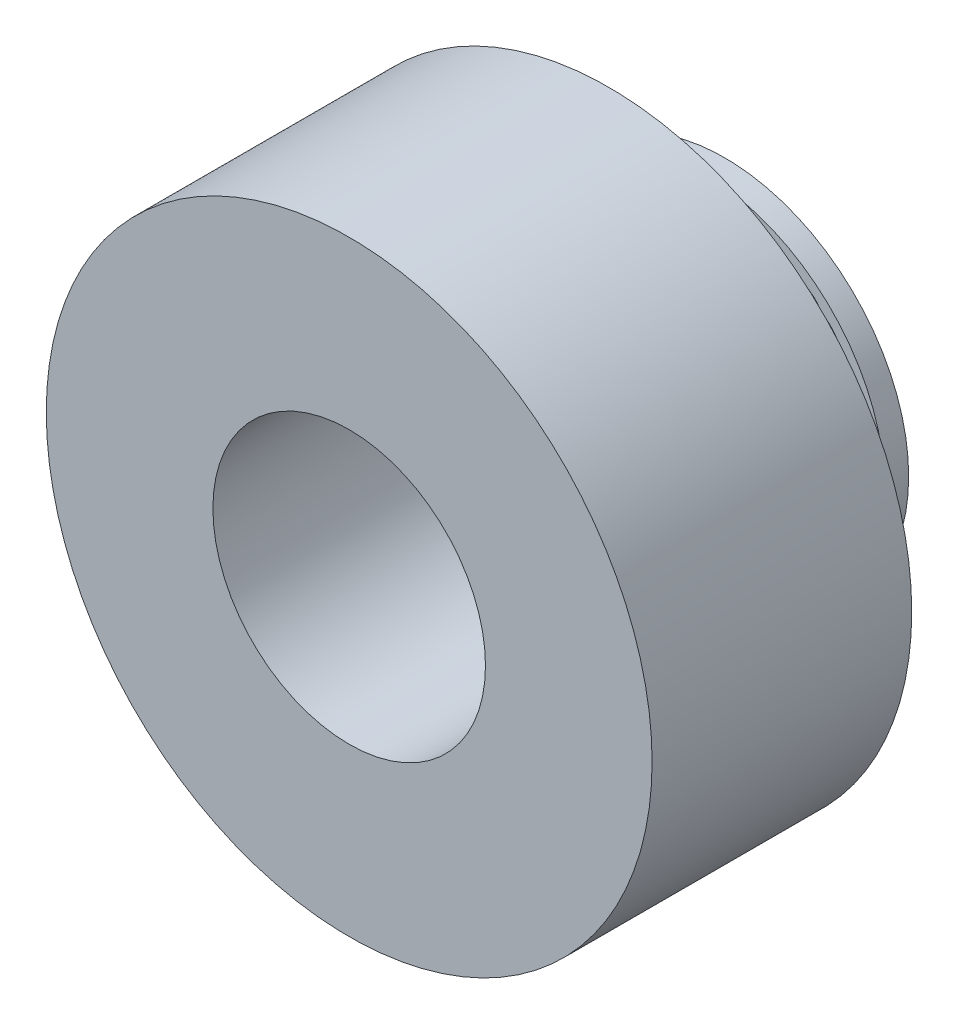
SolidWorks part; units mm, degrees
ref_plane "Front Plane" through (0, 0, 0) normal (0, 0, 1) x (1, 0, 0)
ref_plane "Top Plane" through (0, 0, 0) normal (0, 1, 0) x (1, 0, 0)
ref_plane "Right Plane" through (0, 0, 0) normal (1, 0, 0) x (0, 0, -1)
sketch "Sketch1" plane through (0, 0, 0) normal (0, 0, 1) x (1, 0, 0)
  line L0 (-50.7835, 0) -> (-50.3466, 0)
  line L5 (-50.2571, 0.0627) -> (-50.1641, 0.3183)
  line L6 (-50.0746, 0.381) -> (-49.4934, 0.381)
  line L7 (-49.784, 0.381) -> (-49.784, 0) construction
  line L8 (-49.3109, 0.0627) -> (-49.4039, 0.3183)
  line L39 (-51.2936, 0.1442) -> (-51.3455, 0.4113)
  line L40 (-50.2571, 0.0627) -> (-49.3109, 0.0627) construction
  line L56 (-49.2214, 0) -> (-48.7845, 0)
  line L60 (-51.9981, 0.5781) -> (-51.4241, 0.4872)
  line L61 (-52.2282, 0.2923) -> (-52.0963, 0.5302)
  line L62 (-52.7579, 0.3127) -> (-52.3264, 0.2444)
  line L63 (-51.215, 0.0683) -> (-50.7835, 0)
  line L64 (-53.2392, 0.535) -> (-53.2487, 0.8069)
  line L65 (-53.8671, 1.0737) -> (-53.3144, 0.8941)
  line L66 (-54.1391, 0.8274) -> (-53.9716, 1.0418)
  line L67 (-54.6591, 0.9304) -> (-54.2436, 0.7954)
  line L68 (-53.1734, 0.4477) -> (-52.7579, 0.3127)
  line L69 (-55.0997, 1.2253) -> (-55.0665, 1.4953)
  line L70 (-55.6356, 1.8556) -> (-55.1178, 1.5918)
  line L71 (-55.9428, 1.6549) -> (-55.7438, 1.8404)
  line L72 (-56.4403, 1.838) -> (-56.051, 1.6396)
  line L73 (-55.0484, 1.1288) -> (-54.6591, 0.9304)
  line L74 (-56.8293, 2.1981) -> (-56.7543, 2.4596)
  line L75 (-57.26, 2.9045) -> (-56.7898, 2.5629)
  line L76 (-57.5948, 2.7543) -> (-57.3693, 2.9064)
  line L77 (-58.0575, 3.013) -> (-57.7041, 2.7562)
  line L78 (-56.7937, 2.0948) -> (-56.4403, 1.838)
  line L79 (-58.3854, 3.4295) -> (-58.2704, 3.6761)
  line L80 (-58.7003, 4.1946) -> (-58.2894, 3.7837)
  line L81 (-59.0545, 4.0986) -> (-58.8079, 4.2136)
  line L82 (-59.471, 4.4265) -> (-59.1621, 4.1176)
  line L83 (-58.3664, 3.3219) -> (-58.0575, 3.013)
  line L84 (-59.7297, 4.8892) -> (-59.5776, 5.1147)
  line L85 (-59.9211, 5.6942) -> (-59.5795, 5.224)
  line L86 (-60.2859, 5.6547) -> (-60.0244, 5.7297)
  line L87 (-60.646, 6.0437) -> (-60.3892, 5.6903)
  line L88 (-59.7278, 4.7799) -> (-59.471, 4.4265)
  line L89 (-60.8291, 6.5412) -> (-60.6436, 6.7402)
  line L90 (-60.8922, 7.3662) -> (-60.6284, 6.8484)
  line L91 (-61.2587, 7.3843) -> (-60.9887, 7.4175)
  line L92 (-61.5536, 7.8249) -> (-61.3552, 7.4356)
  line L93 (-60.8444, 6.433) -> (-60.646, 6.0437)
  line L94 (-61.6566, 8.3449) -> (-61.4422, 8.5124)
  line L95 (-61.5899, 9.1696) -> (-61.4103, 8.6169)
  line L96 (-61.949, 9.2448) -> (-61.6771, 9.2353)
  line L97 (-62.1713, 9.7261) -> (-62.0363, 9.3106)
  line L98 (-61.6886, 8.2404) -> (-61.5536, 7.8249)
  line L99 (-62.1917, 10.2558) -> (-61.9538, 10.3877)
  line L100 (-61.9968, 11.0599) -> (-61.9059, 10.4859)
  line L101 (-62.3398, 11.1904) -> (-62.0727, 11.1385)
  line L102 (-62.484, 11.7005) -> (-62.4157, 11.269)
  line L103 (-62.2396, 10.1576) -> (-62.1713, 9.7261)
  line L104 (-62.4213, 12.2269) -> (-62.1657, 12.3199)
  line L105 (-62.103, 12.9906) -> (-62.103, 12.4094)
  line L106 (-62.4213, 13.1731) -> (-62.1657, 13.0801)
  line L107 (-62.484, 13.6995) -> (-62.484, 13.2626)
  line L108 (-62.484, 12.1374) -> (-62.484, 11.7005)
  line L109 (-62.3398, 14.2096) -> (-62.0727, 14.2615)
  line L110 (-61.9059, 14.9141) -> (-61.9968, 14.3401)
  line L111 (-62.1917, 15.1442) -> (-61.9538, 15.0123)
  line L112 (-62.1713, 15.6739) -> (-62.2396, 15.2424)
  line L113 (-62.4157, 14.131) -> (-62.484, 13.6995)
  line L114 (-61.949, 16.1552) -> (-61.6771, 16.1647)
  line L115 (-61.4103, 16.7831) -> (-61.5899, 16.2304)
  line L116 (-61.6566, 17.0551) -> (-61.4422, 16.8876)
  line L117 (-61.5536, 17.5751) -> (-61.6886, 17.1596)
  line L118 (-62.0363, 16.0894) -> (-62.1713, 15.6739)
  line L119 (-61.2587, 18.0157) -> (-60.9887, 17.9825)
  line L120 (-60.6284, 18.5516) -> (-60.8922, 18.0338)
  line L121 (-60.8291, 18.8588) -> (-60.6436, 18.6598)
  line L122 (-60.646, 19.3563) -> (-60.8444, 18.967)
  line L123 (-61.3552, 17.9644) -> (-61.5536, 17.5751)
  line L124 (-60.2859, 19.7453) -> (-60.0244, 19.6703)
  line L125 (-59.5795, 20.176) -> (-59.9211, 19.7058)
  line L126 (-59.7297, 20.5108) -> (-59.5776, 20.2853)
  line L127 (-59.471, 20.9735) -> (-59.7278, 20.6201)
  line L128 (-60.3892, 19.7097) -> (-60.646, 19.3563)
  line L129 (-59.0545, 21.3014) -> (-58.8079, 21.1864)
  line L130 (-58.2894, 21.6163) -> (-58.7003, 21.2054)
  line L131 (-58.3854, 21.9705) -> (-58.2704, 21.7239)
  line L132 (-58.0575, 22.387) -> (-58.3664, 22.0781)
  line L133 (-59.1621, 21.2824) -> (-59.471, 20.9735)
  line L134 (-57.5948, 22.6457) -> (-57.3693, 22.4936)
  line L135 (-56.7898, 22.8371) -> (-57.26, 22.4955)
  line L136 (-56.8293, 23.2019) -> (-56.7543, 22.9404)
  line L137 (-56.4403, 23.562) -> (-56.7937, 23.3052)
  line L138 (-57.7041, 22.6438) -> (-58.0575, 22.387)
  line L139 (-55.9428, 23.7451) -> (-55.7438, 23.5596)
  line L140 (-55.1178, 23.8082) -> (-55.6356, 23.5444)
  line L141 (-55.0997, 24.1747) -> (-55.0665, 23.9047)
  line L142 (-54.6591, 24.4696) -> (-55.0484, 24.2712)
  line L143 (-56.051, 23.7604) -> (-56.4403, 23.562)
  line L144 (-54.1391, 24.5726) -> (-53.9716, 24.3582)
  line L145 (-53.3144, 24.5059) -> (-53.8671, 24.3263)
  line L146 (-53.2392, 24.865) -> (-53.2487, 24.5931)
  line L147 (-52.7579, 25.0873) -> (-53.1734, 24.9523)
  line L148 (-54.2436, 24.6046) -> (-54.6591, 24.4696)
  line L149 (-52.2282, 25.1077) -> (-52.0963, 24.8698)
  line L150 (-51.4241, 24.9128) -> (-51.9981, 24.8219)
  line L151 (-51.2936, 25.2558) -> (-51.3455, 24.9887)
  line L152 (-50.7835, 25.4) -> (-51.215, 25.3317)
  line L153 (-52.3264, 25.1556) -> (-52.7579, 25.0873)
  line L154 (-50.2571, 25.3373) -> (-50.1641, 25.0817)
  line L155 (-49.4934, 25.019) -> (-50.0746, 25.019)
  line L156 (-49.3109, 25.3373) -> (-49.4039, 25.0817)
  line L157 (-48.7845, 25.4) -> (-49.2214, 25.4)
  line L158 (-50.3466, 25.4) -> (-50.7835, 25.4)
  line L159 (-48.2744, 25.2558) -> (-48.2225, 24.9887)
  line L160 (-47.5699, 24.8219) -> (-48.1439, 24.9128)
  line L161 (-47.3398, 25.1077) -> (-47.4717, 24.8698)
  line L162 (-46.8101, 25.0873) -> (-47.2416, 25.1556)
  line L163 (-48.353, 25.3317) -> (-48.7845, 25.4)
  line L164 (-46.3288, 24.865) -> (-46.3193, 24.5931)
  line L165 (-45.7009, 24.3263) -> (-46.2536, 24.5059)
  line L166 (-45.4289, 24.5726) -> (-45.5964, 24.3582)
  line L167 (-44.9089, 24.4696) -> (-45.3244, 24.6046)
  line L168 (-46.3946, 24.9523) -> (-46.8101, 25.0873)
  line L169 (-44.4683, 24.1747) -> (-44.5015, 23.9047)
  line L170 (-43.9324, 23.5444) -> (-44.4502, 23.8082)
  line L171 (-43.6252, 23.7451) -> (-43.8242, 23.5596)
  line L172 (-43.1277, 23.562) -> (-43.517, 23.7604)
  line L173 (-44.5196, 24.2712) -> (-44.9089, 24.4696)
  line L174 (-42.7387, 23.2019) -> (-42.8137, 22.9404)
  line L175 (-42.308, 22.4955) -> (-42.7782, 22.8371)
  line L176 (-41.9732, 22.6457) -> (-42.1987, 22.4936)
  line L177 (-41.5105, 22.387) -> (-41.8639, 22.6438)
  line L178 (-42.7743, 23.3052) -> (-43.1277, 23.562)
  line L179 (-41.1826, 21.9705) -> (-41.2976, 21.7239)
  line L180 (-40.8677, 21.2054) -> (-41.2786, 21.6163)
  line L181 (-40.5135, 21.3014) -> (-40.7601, 21.1864)
  line L182 (-40.097, 20.9735) -> (-40.4059, 21.2824)
  line L183 (-41.2016, 22.0781) -> (-41.5105, 22.387)
  line L184 (-39.8383, 20.5108) -> (-39.9904, 20.2853)
  line L185 (-39.6469, 19.7058) -> (-39.9885, 20.176)
  line L186 (-39.2821, 19.7453) -> (-39.5436, 19.6703)
  line L187 (-38.922, 19.3563) -> (-39.1788, 19.7097)
  line L188 (-39.8402, 20.6201) -> (-40.097, 20.9735)
  line L189 (-38.7389, 18.8588) -> (-38.9244, 18.6598)
  line L190 (-38.6758, 18.0338) -> (-38.9396, 18.5516)
  line L191 (-38.3093, 18.0157) -> (-38.5793, 17.9825)
  line L192 (-38.0144, 17.5751) -> (-38.2128, 17.9644)
  line L193 (-38.7236, 18.967) -> (-38.922, 19.3563)
  line L194 (-37.9114, 17.0551) -> (-38.1258, 16.8876)
  line L195 (-37.9781, 16.2304) -> (-38.1577, 16.7831)
  line L196 (-37.619, 16.1552) -> (-37.8909, 16.1647)
  line L197 (-37.3967, 15.6739) -> (-37.5317, 16.0894)
  line L198 (-37.8794, 17.1596) -> (-38.0144, 17.5751)
  line L199 (-37.3763, 15.1442) -> (-37.6142, 15.0123)
  line L200 (-37.5712, 14.3401) -> (-37.6621, 14.9141)
  line L201 (-37.2282, 14.2096) -> (-37.4953, 14.2615)
  line L202 (-37.084, 13.6995) -> (-37.1523, 14.131)
  line L203 (-37.3284, 15.2424) -> (-37.3967, 15.6739)
  line L204 (-37.1467, 13.1731) -> (-37.4023, 13.0801)
  line L205 (-37.465, 12.4094) -> (-37.465, 12.9906)
  line L206 (-37.1467, 12.2269) -> (-37.4023, 12.3199)
  line L207 (-37.084, 11.7005) -> (-37.084, 12.1374)
  line L208 (-37.084, 13.2626) -> (-37.084, 13.6995)
  line L209 (-37.2282, 11.1904) -> (-37.4953, 11.1385)
  line L210 (-37.6621, 10.4859) -> (-37.5712, 11.0599)
  line L211 (-37.3763, 10.2558) -> (-37.6142, 10.3877)
  line L212 (-37.3967, 9.7261) -> (-37.3284, 10.1576)
  line L213 (-37.1523, 11.269) -> (-37.084, 11.7005)
  line L214 (-37.619, 9.2448) -> (-37.8909, 9.2353)
  line L215 (-38.1577, 8.6169) -> (-37.9781, 9.1696)
  line L216 (-37.9114, 8.3449) -> (-38.1258, 8.5124)
  line L217 (-38.0144, 7.8249) -> (-37.8794, 8.2404)
  line L218 (-37.5317, 9.3106) -> (-37.3967, 9.7261)
  line L219 (-38.3093, 7.3843) -> (-38.5793, 7.4175)
  line L220 (-38.9396, 6.8484) -> (-38.6758, 7.3662)
  line L221 (-38.7389, 6.5412) -> (-38.9244, 6.7402)
  line L222 (-38.922, 6.0437) -> (-38.7236, 6.433)
  line L223 (-38.2128, 7.4356) -> (-38.0144, 7.8249)
  line L224 (-39.2821, 5.6547) -> (-39.5436, 5.7297)
  line L225 (-39.9885, 5.224) -> (-39.6469, 5.6942)
  line L226 (-39.8383, 4.8892) -> (-39.9904, 5.1147)
  line L227 (-40.097, 4.4265) -> (-39.8402, 4.7799)
  line L228 (-39.1788, 5.6903) -> (-38.922, 6.0437)
  line L229 (-40.5135, 4.0986) -> (-40.7601, 4.2136)
  line L230 (-41.2786, 3.7837) -> (-40.8677, 4.1946)
  line L231 (-41.1826, 3.4295) -> (-41.2976, 3.6761)
  line L232 (-41.5105, 3.013) -> (-41.2016, 3.3219)
  line L233 (-40.4059, 4.1176) -> (-40.097, 4.4265)
  line L234 (-41.9732, 2.7543) -> (-42.1987, 2.9064)
  line L235 (-42.7782, 2.5629) -> (-42.308, 2.9045)
  line L236 (-42.7387, 2.1981) -> (-42.8137, 2.4596)
  line L237 (-43.1277, 1.838) -> (-42.7743, 2.0948)
  line L238 (-41.8639, 2.7562) -> (-41.5105, 3.013)
  line L239 (-43.6252, 1.6549) -> (-43.8242, 1.8404)
  line L240 (-44.4502, 1.5918) -> (-43.9324, 1.8556)
  line L241 (-44.4683, 1.2253) -> (-44.5015, 1.4953)
  line L242 (-44.9089, 0.9304) -> (-44.5196, 1.1288)
  line L243 (-43.517, 1.6396) -> (-43.1277, 1.838)
  line L244 (-45.4289, 0.8274) -> (-45.5964, 1.0418)
  line L245 (-46.2536, 0.8941) -> (-45.7009, 1.0737)
  line L246 (-46.3288, 0.535) -> (-46.3193, 0.8069)
  line L247 (-46.8101, 0.3127) -> (-46.3946, 0.4477)
  line L248 (-45.3244, 0.7954) -> (-44.9089, 0.9304)
  line L249 (-47.3398, 0.2923) -> (-47.4717, 0.5302)
  line L250 (-48.1439, 0.4872) -> (-47.5699, 0.5781)
  line L251 (-48.2744, 0.1442) -> (-48.2225, 0.4113)
  line L252 (-48.7845, 0) -> (-48.353, 0.0683)
  line L253 (-47.2416, 0.2444) -> (-46.8101, 0.3127)
  arc A0 (-50.3466, 0) -> (-50.2571, 0.0627) centre (-50.3466, 0.0952) ccw
  arc A1 (-50.1641, 0.3183) -> (-50.0746, 0.381) centre (-50.0746, 0.2857) cw
  arc A2 (-49.4039, 0.3183) -> (-49.4934, 0.381) centre (-49.4934, 0.2857) ccw
  arc A3 (-49.2214, 0) -> (-49.3109, 0.0627) centre (-49.2214, 0.0952) cw
  arc A4 (-51.215, 0.0683) -> (-51.2936, 0.1442) centre (-51.2001, 0.1624) cw
  arc A5 (-51.3455, 0.4113) -> (-51.4241, 0.4872) centre (-51.439, 0.3931) ccw
  arc A6 (-52.0963, 0.5302) -> (-51.9981, 0.5781) centre (-52.013, 0.484) cw
  arc A7 (-52.3264, 0.2444) -> (-52.2282, 0.2923) centre (-52.3115, 0.3385) ccw
  arc A8 (-53.1734, 0.4477) -> (-53.2392, 0.535) centre (-53.144, 0.5383) cw
  arc A9 (-53.2487, 0.8069) -> (-53.3144, 0.8941) centre (-53.3439, 0.8036) ccw
  arc A10 (-53.9716, 1.0418) -> (-53.8671, 1.0737) centre (-53.8966, 0.9831) cw
  arc A11 (-54.2436, 0.7954) -> (-54.1391, 0.8274) centre (-54.2142, 0.886) ccw
  arc A12 (-55.0484, 1.1288) -> (-55.0997, 1.2253) centre (-55.0051, 1.2137) cw
  arc A13 (-55.0665, 1.4953) -> (-55.1178, 1.5918) centre (-55.1611, 1.5069) ccw
  arc A14 (-55.7438, 1.8404) -> (-55.6356, 1.8556) centre (-55.6789, 1.7707) cw
  arc A15 (-56.051, 1.6396) -> (-55.9428, 1.6549) centre (-56.0077, 1.7245) ccw
  arc A16 (-56.7937, 2.0948) -> (-56.8293, 2.1981) centre (-56.7377, 2.1718) cw
  arc A17 (-56.7543, 2.4596) -> (-56.7898, 2.5629) centre (-56.8458, 2.4859) ccw
  arc A18 (-57.3693, 2.9064) -> (-57.26, 2.9045) centre (-57.316, 2.8275) cw
  arc A19 (-57.7041, 2.7562) -> (-57.5948, 2.7543) centre (-57.6481, 2.8333) ccw
  arc A20 (-58.3664, 3.3219) -> (-58.3854, 3.4295) centre (-58.2991, 3.3893) cw
  arc A21 (-58.2704, 3.6761) -> (-58.2894, 3.7837) centre (-58.3567, 3.7163) ccw
  arc A22 (-58.8079, 4.2136) -> (-58.7003, 4.1946) centre (-58.7677, 4.1273) cw
  arc A23 (-59.1621, 4.1176) -> (-59.0545, 4.0986) centre (-59.0947, 4.1849) ccw
  arc A24 (-59.7278, 4.7799) -> (-59.7297, 4.8892) centre (-59.6507, 4.8359) cw
  arc A25 (-59.5776, 5.1147) -> (-59.5795, 5.224) centre (-59.6565, 5.168) ccw
  arc A26 (-60.0244, 5.7297) -> (-59.9211, 5.6942) centre (-59.9981, 5.6382) cw
  arc A27 (-60.3892, 5.6903) -> (-60.2859, 5.6547) centre (-60.3122, 5.7463) ccw
  arc A28 (-60.8444, 6.433) -> (-60.8291, 6.5412) centre (-60.7595, 6.4763) cw
  arc A29 (-60.6436, 6.7402) -> (-60.6284, 6.8484) centre (-60.7133, 6.8051) ccw
  arc A30 (-60.9887, 7.4175) -> (-60.8922, 7.3662) centre (-60.9771, 7.3229) cw
  arc A31 (-61.3552, 7.4356) -> (-61.2587, 7.3843) centre (-61.2703, 7.4789) ccw
  arc A32 (-61.6886, 8.2404) -> (-61.6566, 8.3449) centre (-61.598, 8.2698) cw
  arc A33 (-61.4422, 8.5124) -> (-61.4103, 8.6169) centre (-61.5009, 8.5874) ccw
  arc A34 (-61.6771, 9.2353) -> (-61.5899, 9.1696) centre (-61.6804, 9.1401) cw
  arc A35 (-62.0363, 9.3106) -> (-61.949, 9.2448) centre (-61.9457, 9.34) ccw
  arc A36 (-62.2396, 10.1576) -> (-62.1917, 10.2558) centre (-62.1455, 10.1725) cw
  arc A37 (-61.9538, 10.3877) -> (-61.9059, 10.4859) centre (-62, 10.471) ccw
  arc A38 (-62.0727, 11.1385) -> (-61.9968, 11.0599) centre (-62.0909, 11.045) cw
  arc A39 (-62.4157, 11.269) -> (-62.3398, 11.1904) centre (-62.3216, 11.2839) ccw
  arc A40 (-62.484, 12.1374) -> (-62.4213, 12.2269) centre (-62.3888, 12.1374) cw
  arc A41 (-62.1657, 12.3199) -> (-62.103, 12.4094) centre (-62.1983, 12.4094) ccw
  arc A42 (-62.1657, 13.0801) -> (-62.103, 12.9906) centre (-62.1983, 12.9906) cw
  arc A43 (-62.484, 13.2626) -> (-62.4213, 13.1731) centre (-62.3888, 13.2626) ccw
  arc A44 (-62.4157, 14.131) -> (-62.3398, 14.2096) centre (-62.3216, 14.1161) cw
  arc A45 (-62.0727, 14.2615) -> (-61.9968, 14.3401) centre (-62.0909, 14.355) ccw
  arc A46 (-61.9538, 15.0123) -> (-61.9059, 14.9141) centre (-62, 14.929) cw
  arc A47 (-62.2396, 15.2424) -> (-62.1917, 15.1442) centre (-62.1455, 15.2275) ccw
  arc A48 (-62.0363, 16.0894) -> (-61.949, 16.1552) centre (-61.9457, 16.06) cw
  arc A49 (-61.6771, 16.1647) -> (-61.5899, 16.2304) centre (-61.6804, 16.2599) ccw
  arc A50 (-61.4422, 16.8876) -> (-61.4103, 16.7831) centre (-61.5009, 16.8126) cw
  arc A51 (-61.6886, 17.1596) -> (-61.6566, 17.0551) centre (-61.598, 17.1302) ccw
  arc A52 (-61.3552, 17.9644) -> (-61.2587, 18.0157) centre (-61.2703, 17.9211) cw
  arc A53 (-60.9887, 17.9825) -> (-60.8922, 18.0338) centre (-60.9771, 18.0771) ccw
  arc A54 (-60.6436, 18.6598) -> (-60.6284, 18.5516) centre (-60.7133, 18.5949) cw
  arc A55 (-60.8444, 18.967) -> (-60.8291, 18.8588) centre (-60.7595, 18.9237) ccw
  arc A56 (-60.3892, 19.7097) -> (-60.2859, 19.7453) centre (-60.3122, 19.6537) cw
  arc A57 (-60.0244, 19.6703) -> (-59.9211, 19.7058) centre (-59.9981, 19.7618) ccw
  arc A58 (-59.5776, 20.2853) -> (-59.5795, 20.176) centre (-59.6565, 20.232) cw
  arc A59 (-59.7278, 20.6201) -> (-59.7297, 20.5108) centre (-59.6507, 20.5641) ccw
  arc A60 (-59.1621, 21.2824) -> (-59.0545, 21.3014) centre (-59.0947, 21.2151) cw
  arc A61 (-58.8079, 21.1864) -> (-58.7003, 21.2054) centre (-58.7677, 21.2727) ccw
  arc A62 (-58.2704, 21.7239) -> (-58.2894, 21.6163) centre (-58.3567, 21.6837) cw
  arc A63 (-58.3664, 22.0781) -> (-58.3854, 21.9705) centre (-58.2991, 22.0107) ccw
  arc A64 (-57.7041, 22.6438) -> (-57.5948, 22.6457) centre (-57.6481, 22.5667) cw
  arc A65 (-57.3693, 22.4936) -> (-57.26, 22.4955) centre (-57.316, 22.5725) ccw
  arc A66 (-56.7543, 22.9404) -> (-56.7898, 22.8371) centre (-56.8458, 22.9141) cw
  arc A67 (-56.7937, 23.3052) -> (-56.8293, 23.2019) centre (-56.7377, 23.2282) ccw
  arc A68 (-56.051, 23.7604) -> (-55.9428, 23.7451) centre (-56.0077, 23.6755) cw
  arc A69 (-55.7438, 23.5596) -> (-55.6356, 23.5444) centre (-55.6789, 23.6293) ccw
  arc A70 (-55.0665, 23.9047) -> (-55.1178, 23.8082) centre (-55.1611, 23.8931) cw
  arc A71 (-55.0484, 24.2712) -> (-55.0997, 24.1747) centre (-55.0051, 24.1863) ccw
  arc A72 (-54.2436, 24.6046) -> (-54.1391, 24.5726) centre (-54.2142, 24.514) cw
  arc A73 (-53.9716, 24.3582) -> (-53.8671, 24.3263) centre (-53.8966, 24.4169) ccw
  arc A74 (-53.2487, 24.5931) -> (-53.3144, 24.5059) centre (-53.3439, 24.5964) cw
  arc A75 (-53.1734, 24.9523) -> (-53.2392, 24.865) centre (-53.144, 24.8617) ccw
  arc A76 (-52.3264, 25.1556) -> (-52.2282, 25.1077) centre (-52.3115, 25.0615) cw
  arc A77 (-52.0963, 24.8698) -> (-51.9981, 24.8219) centre (-52.013, 24.916) ccw
  arc A78 (-51.3455, 24.9887) -> (-51.4241, 24.9128) centre (-51.439, 25.0069) cw
  arc A79 (-51.215, 25.3317) -> (-51.2936, 25.2558) centre (-51.2001, 25.2376) ccw
  arc A80 (-50.3466, 25.4) -> (-50.2571, 25.3373) centre (-50.3466, 25.3048) cw
  arc A81 (-50.1641, 25.0817) -> (-50.0746, 25.019) centre (-50.0746, 25.1143) ccw
  arc A82 (-49.4039, 25.0817) -> (-49.4934, 25.019) centre (-49.4934, 25.1143) cw
  arc A83 (-49.2214, 25.4) -> (-49.3109, 25.3373) centre (-49.2214, 25.3048) ccw
  arc A84 (-48.353, 25.3317) -> (-48.2744, 25.2558) centre (-48.3679, 25.2376) cw
  arc A85 (-48.2225, 24.9887) -> (-48.1439, 24.9128) centre (-48.129, 25.0069) ccw
  arc A86 (-47.4717, 24.8698) -> (-47.5699, 24.8219) centre (-47.555, 24.916) cw
  arc A87 (-47.2416, 25.1556) -> (-47.3398, 25.1077) centre (-47.2565, 25.0615) ccw
  arc A88 (-46.3946, 24.9523) -> (-46.3288, 24.865) centre (-46.424, 24.8617) cw
  arc A89 (-46.3193, 24.5931) -> (-46.2536, 24.5059) centre (-46.2241, 24.5964) ccw
  arc A90 (-45.5964, 24.3582) -> (-45.7009, 24.3263) centre (-45.6714, 24.4169) cw
  arc A91 (-45.3244, 24.6046) -> (-45.4289, 24.5726) centre (-45.3538, 24.514) ccw
  arc A92 (-44.5196, 24.2712) -> (-44.4683, 24.1747) centre (-44.5629, 24.1863) cw
  arc A93 (-44.5015, 23.9047) -> (-44.4502, 23.8082) centre (-44.4069, 23.8931) ccw
  arc A94 (-43.8242, 23.5596) -> (-43.9324, 23.5444) centre (-43.8891, 23.6293) cw
  arc A95 (-43.517, 23.7604) -> (-43.6252, 23.7451) centre (-43.5603, 23.6755) ccw
  arc A96 (-42.7743, 23.3052) -> (-42.7387, 23.2019) centre (-42.8303, 23.2282) cw
  arc A97 (-42.8137, 22.9404) -> (-42.7782, 22.8371) centre (-42.7222, 22.9141) ccw
  arc A98 (-42.1987, 22.4936) -> (-42.308, 22.4955) centre (-42.252, 22.5725) cw
  arc A99 (-41.8639, 22.6438) -> (-41.9732, 22.6457) centre (-41.9199, 22.5667) ccw
  arc A100 (-41.2016, 22.0781) -> (-41.1826, 21.9705) centre (-41.2689, 22.0107) cw
  arc A101 (-41.2976, 21.7239) -> (-41.2786, 21.6163) centre (-41.2113, 21.6837) ccw
  arc A102 (-40.7601, 21.1864) -> (-40.8677, 21.2054) centre (-40.8003, 21.2727) cw
  arc A103 (-40.4059, 21.2824) -> (-40.5135, 21.3014) centre (-40.4733, 21.2151) ccw
  arc A104 (-39.8402, 20.6201) -> (-39.8383, 20.5108) centre (-39.9173, 20.5641) cw
  arc A105 (-39.9904, 20.2853) -> (-39.9885, 20.176) centre (-39.9115, 20.232) ccw
  arc A106 (-39.5436, 19.6703) -> (-39.6469, 19.7058) centre (-39.5699, 19.7618) cw
  arc A107 (-39.1788, 19.7097) -> (-39.2821, 19.7453) centre (-39.2558, 19.6537) ccw
  arc A108 (-38.7236, 18.967) -> (-38.7389, 18.8588) centre (-38.8085, 18.9237) cw
  arc A109 (-38.9244, 18.6598) -> (-38.9396, 18.5516) centre (-38.8547, 18.5949) ccw
  arc A110 (-38.5793, 17.9825) -> (-38.6758, 18.0338) centre (-38.5909, 18.0771) cw
  arc A111 (-38.2128, 17.9644) -> (-38.3093, 18.0157) centre (-38.2977, 17.9211) ccw
  arc A112 (-37.8794, 17.1596) -> (-37.9114, 17.0551) centre (-37.97, 17.1302) cw
  arc A113 (-38.1258, 16.8876) -> (-38.1577, 16.7831) centre (-38.0671, 16.8126) ccw
  arc A114 (-37.8909, 16.1647) -> (-37.9781, 16.2304) centre (-37.8876, 16.2599) cw
  arc A115 (-37.5317, 16.0894) -> (-37.619, 16.1552) centre (-37.6223, 16.06) ccw
  arc A116 (-37.3284, 15.2424) -> (-37.3763, 15.1442) centre (-37.4225, 15.2275) cw
  arc A117 (-37.6142, 15.0123) -> (-37.6621, 14.9141) centre (-37.568, 14.929) ccw
  arc A118 (-37.4953, 14.2615) -> (-37.5712, 14.3401) centre (-37.4771, 14.355) cw
  arc A119 (-37.1523, 14.131) -> (-37.2282, 14.2096) centre (-37.2464, 14.1161) ccw
  arc A120 (-37.084, 13.2626) -> (-37.1467, 13.1731) centre (-37.1792, 13.2626) cw
  arc A121 (-37.4023, 13.0801) -> (-37.465, 12.9906) centre (-37.3697, 12.9906) ccw
  arc A122 (-37.4023, 12.3199) -> (-37.465, 12.4094) centre (-37.3698, 12.4094) cw
  arc A123 (-37.084, 12.1374) -> (-37.1467, 12.2269) centre (-37.1792, 12.1374) ccw
  arc A124 (-37.1523, 11.269) -> (-37.2282, 11.1904) centre (-37.2464, 11.2839) cw
  arc A125 (-37.4953, 11.1385) -> (-37.5712, 11.0599) centre (-37.4771, 11.045) ccw
  arc A126 (-37.6142, 10.3877) -> (-37.6621, 10.4859) centre (-37.568, 10.471) cw
  arc A127 (-37.3284, 10.1576) -> (-37.3763, 10.2558) centre (-37.4225, 10.1725) ccw
  arc A128 (-37.5317, 9.3106) -> (-37.619, 9.2448) centre (-37.6223, 9.34) cw
  arc A129 (-37.8909, 9.2353) -> (-37.9781, 9.1696) centre (-37.8876, 9.1401) ccw
  arc A130 (-38.1258, 8.5124) -> (-38.1577, 8.6169) centre (-38.0671, 8.5874) cw
  arc A131 (-37.8794, 8.2404) -> (-37.9114, 8.3449) centre (-37.97, 8.2698) ccw
  arc A132 (-38.2128, 7.4356) -> (-38.3093, 7.3843) centre (-38.2977, 7.4789) cw
  arc A133 (-38.5793, 7.4175) -> (-38.6758, 7.3662) centre (-38.5909, 7.3229) ccw
  arc A134 (-38.9244, 6.7402) -> (-38.9396, 6.8484) centre (-38.8547, 6.8051) cw
  arc A135 (-38.7236, 6.433) -> (-38.7389, 6.5412) centre (-38.8085, 6.4763) ccw
  arc A136 (-39.1788, 5.6903) -> (-39.2821, 5.6547) centre (-39.2558, 5.7463) cw
  arc A137 (-39.5436, 5.7297) -> (-39.6469, 5.6942) centre (-39.5699, 5.6382) ccw
  arc A138 (-39.9904, 5.1147) -> (-39.9885, 5.224) centre (-39.9115, 5.168) cw
  arc A139 (-39.8402, 4.7799) -> (-39.8383, 4.8892) centre (-39.9173, 4.8359) ccw
  arc A140 (-40.4059, 4.1176) -> (-40.5135, 4.0986) centre (-40.4733, 4.1849) cw
  arc A141 (-40.7601, 4.2136) -> (-40.8677, 4.1946) centre (-40.8003, 4.1273) ccw
  arc A142 (-41.2976, 3.6761) -> (-41.2786, 3.7837) centre (-41.2113, 3.7163) cw
  arc A143 (-41.2016, 3.3219) -> (-41.1826, 3.4295) centre (-41.2689, 3.3893) ccw
  arc A144 (-41.8639, 2.7562) -> (-41.9732, 2.7543) centre (-41.9199, 2.8333) cw
  arc A145 (-42.1987, 2.9064) -> (-42.308, 2.9045) centre (-42.252, 2.8275) ccw
  arc A146 (-42.8137, 2.4596) -> (-42.7782, 2.5629) centre (-42.7222, 2.4859) cw
  arc A147 (-42.7743, 2.0948) -> (-42.7387, 2.1981) centre (-42.8303, 2.1718) ccw
  arc A148 (-43.517, 1.6396) -> (-43.6252, 1.6549) centre (-43.5603, 1.7245) cw
  arc A149 (-43.8242, 1.8404) -> (-43.9324, 1.8556) centre (-43.8891, 1.7707) ccw
  arc A150 (-44.5015, 1.4953) -> (-44.4502, 1.5918) centre (-44.4069, 1.5069) cw
  arc A151 (-44.5196, 1.1288) -> (-44.4683, 1.2253) centre (-44.5629, 1.2137) ccw
  arc A152 (-45.3244, 0.7954) -> (-45.4289, 0.8274) centre (-45.3538, 0.886) cw
  arc A153 (-45.5964, 1.0418) -> (-45.7009, 1.0737) centre (-45.6714, 0.9831) ccw
  arc A154 (-46.3193, 0.8069) -> (-46.2536, 0.8941) centre (-46.2241, 0.8036) cw
  arc A155 (-46.3946, 0.4477) -> (-46.3288, 0.535) centre (-46.424, 0.5383) ccw
  arc A156 (-47.2416, 0.2444) -> (-47.3398, 0.2923) centre (-47.2565, 0.3385) cw
  arc A157 (-47.4717, 0.5302) -> (-47.5699, 0.5781) centre (-47.555, 0.484) ccw
  arc A158 (-48.2225, 0.4113) -> (-48.1439, 0.4872) centre (-48.129, 0.3931) cw
  arc A159 (-48.353, 0.0683) -> (-48.2744, 0.1442) centre (-48.3679, 0.1624) ccw
  point P1 (-50.292, 0.0172)
  point P2 (-49.784, 12.7)
  point P7 (-49.276, 0.0172)
  point P570 (-49.784, 12.7)
  dimension "D1" = 0.0953
  dimension "D2" = 40
  dimension "D3" = 40
  dimension "D4" = 1.016
  dimension "D7" = 0.381
sketch "Sketch2" plane through (0, 0, 0) normal (0, 0, 1) x (1, 0, 0)
  point P0 (-49.784, 12.7)
extrude "Boss-Extrude1" add sketch "Sketch1" along normal blind 5
sketch "Sketch3" plane through (0, 0, 5) normal (0, 0, 1) x (1, 0, 0)
  circle A0 centre (-49.784, 12.7) radius 13.5
extrude "Boss-Extrude2" add sketch "Sketch3" along normal blind 1.75
sketch "Sketch4" plane through (0, 0, 0) normal (0, 0, -1) x (-1, 0, 0)
  circle A0 centre (49.784, 12.7) radius 13.5
extrude "Boss-Extrude3" add sketch "Sketch4" along normal blind 1.75
sketch "Sketch5" plane through (0, 0, 6.75) normal (0, 0, 1) x (1, 0, 0)
  circle A0 centre (-49.784, 12.7) radius 22.225
  circle A1 centre (-49.784, 12.7) radius 10
  dimension "D1" = 44.45
  dimension "D2" = 20
extrude "Boss-Extrude4" add sketch "Sketch5" along normal blind 19.05
fillet "Fillet1" radius 3.175 1 edges at (-36.284, 12.7, 6.75)
sketch "Sketch6" plane through (0, 0, -1.75) normal (0, 0, -1) x (-1, 0, 0)
  line L0 (48.459, 11.2019) -> (51.109, 11.2019)
  arc A0 (51.109, 11.2019) -> (48.459, 11.2019) centre (49.784, 12.7) ccw
  dimension "D1" = 4
  dimension "D2" = 2.65
extrude "Cut-Extrude1" cut sketch "Sketch6" against normal blind 19.05
